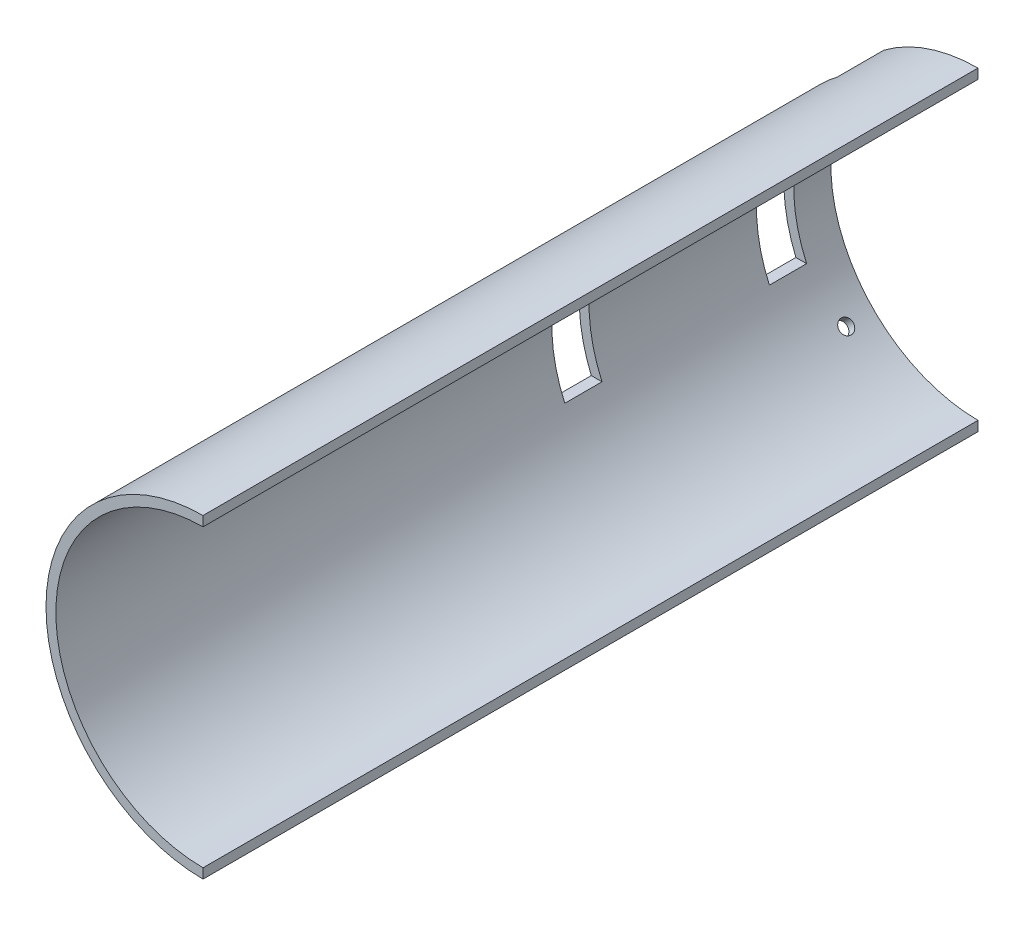
SolidWorks part; units mm, degrees
material "1060 Alloy"
ref_plane "Front Plane" through (0, 0, 0) normal (0, 0, 1) x (1, 0, 0)
ref_plane "Top Plane" through (0, 0, 0) normal (0, 1, 0) x (1, 0, 0)
ref_plane "Right Plane" through (0, 0, 0) normal (1, 0, 0) x (0, 0, -1)
sketch "Sketch1" plane through (0, 0, 0) normal (0, 0, 1) x (1, 0, 0)
  line L0 (0, 50.8) -> (0, 47.62)
  line L1 (0, -47.62) -> (0, -50.8)
  arc A0 (0, 50.8) -> (0, -50.8) centre (0, 0) ccw
  arc A1 (0, 47.62) -> (0, -47.62) centre (0, 0) ccw
  circle A2 centre (0, 0) radius 50.8 construction
  circle A3 centre (0, 0) radius 47.62 construction
  dimension "D1" = 101.6
  dimension "D2" = 3.18
extrude "Boss-Extrude1" add sketch "Sketch1" along normal blind 250
ref_plane "Plane1" through (-35.921, 35.921, 0) normal (-0.7071, 0.7071, 0) x (0, 0, -1)
ref_plane "Plane2" through (-35.921, -35.921, 0) normal (-0.7071, -0.7071, 0) x (0, 0, -1)
sketch "Sketch4" plane through (0, 0, 250) normal (0, 0, 1) x (1, 0, 0)
  line L0 (0, 0) -> (-35.921, 35.921)
  line L1 (-16.1645, 55.6776) -> (-55.6776, 16.1645) construction
  line L2 (0, 0) -> (-35.921, -35.921)
  arc A0 (0, 50.8) -> (0, -50.8) centre (0, 0) ccw construction
hole_wizard "M4 Clearance Hole1" positions "Sketch6" profile "Sketch5" hole size "M4" standard "ISO"
sketch "Sketch6" plane through (-35.921, 35.921, 0) normal (-0.7071, 0.7071, 0) x (0, 0, -1)
  line L1 (0, -35.921) -> (0, 50.8) construction
  point P0 (-9, 0)
  dimension "D1" = 9
sketch "Sketch5" plane through (-35.921, 35.921, 9) normal (0, 0, 1) x (-0.7071, -0.7071, 0)
  line L0 (0, 0) -> (0, 16.3519)
  line L1 (0, 16.3519) -> (2.25, 15)
  line L2 (2.25, 15) -> (2.25, 0)
  line L5 (2.25, 0) -> (0, 0)
  line L10 (0, 16.3519) -> (-2.25, 15) construction
  line L11 (0, -6.35) -> (0, 107.95) construction
  dimension "Hole Dia." = 4.5
  dimension "Hole Depth" = 15
  dimension "Drill Angle" = 118
hole_wizard "M4 Clearance Hole2" positions "Sketch8" profile "Sketch7" hole size "M4" standard "ISO"
sketch "Sketch8" plane through (-35.921, -35.921, 0) normal (-0.7071, -0.7071, 0) x (0, 0, -1)
  line L1 (0, -50.8) -> (0, 35.921) construction
  point P0 (-9, 0)
  dimension "D1" = 9
sketch "Sketch7" plane through (-35.921, -35.921, 9) normal (0, 0, 1) x (0.7071, -0.7071, 0)
  line L0 (0, 0) -> (0, 16.3519)
  line L1 (0, 16.3519) -> (2.25, 15)
  line L2 (2.25, 15) -> (2.25, 0)
  line L5 (2.25, 0) -> (0, 0)
  line L10 (0, 16.3519) -> (-2.25, 15) construction
  line L11 (0, -6.35) -> (0, 107.95) construction
  dimension "Hole Dia." = 4.5
  dimension "Hole Depth" = 15
  dimension "Drill Angle" = 118
ref_plane "Plane3" through (-50.8, 0, 0) normal (-1, 0, 0) x (0, 0, 1)
sketch "Sketch9" plane through (-50.8, 0, 0) normal (-1, 0, 0) x (0, 0, 1)
  line L0 (250, -50.8) -> (250, 50.8) construction
  line L1 (78, 19.5) -> (90, 19.5)
  line L2 (78, 19.5) -> (78, -19.5)
  line L3 (78, 0) -> (90, 0)
  line L4 (90, 19.5) -> (90, -19.5)
  line L5 (78, -19.5) -> (90, -19.5)
  line L6 (0, 0) -> (12, 0)
  line L7 (12, 0) -> (12, 19.5)
  line L8 (12, 19.5) -> (24, 19.5)
  line L9 (24, 19.5) -> (24, -19.5)
  line L10 (24, -19.5) -> (12, -19.5)
  line L11 (12, -19.5) -> (12, 0)
  dimension "D1" = 12
  dimension "D2" = 160
  dimension "D3" = 19.5
  dimension "D4" = 0
  dimension "D5" = 12
  dimension "D6" = 12
extrude "Cut-Extrude1" cut sketch "Sketch9" against normal blind 10 contours L4 L1 L2 L3 | L2 L5 L4 L3 | L11 L10 L9 L8 L7 region at (-50.8, 9.75, 84) region at (-50.8, -9.75, 84) region at (-50.8, 0, 18)
sketch "Sketch12" plane through (-35.921, 35.921, 0) normal (-0.7071, 0.7071, 0) x (0, 0, -1)
  line L0 (-6.75, 0) -> (0, 0)
  circle A0 centre (-9, 0) radius 2.25 construction
sketch "Sketch13" plane through (-35.921, -35.921, 0) normal (-0.7071, -0.7071, 0) x (0, 0, -1)
  line L0 (-6.75, 0) -> (0, 0)
  circle A0 centre (-9, 0) radius 2.25 construction
  circle A1 centre (-9, 0) radius 2.25 construction
sketch "Sketch14" plane through (0, 0, 0) normal (0, 0, -1) x (-1, 0, 0)
  line L0 (35.9241, 35.9179) -> (35.5706, 35.5644)
  line L1 (30.54, 40.5949) -> (40.5949, 30.54)
  line L3 (32.2061, 39.2833) -> (39.2833, 32.2061)
  arc A0 (0, -50.8) -> (0, 50.8) centre (0, 0) ccw construction
  arc A1 (39.2833, 32.2061) -> (32.2061, 39.2833) centre (0, 0) ccw
  circle A2 centre (0, 0) radius 50.8
  arc M2 (0, -50.8) -> (0, 50.8) centre (0, 0) ccw
  dimension "D1" = 0.5
extrude "Cut-Extrude2" cut sketch "Sketch14" against normal blind 15 contours L0 A1 L3 | L3 A1 L0 | A1 L3 L0 L1 M2 | A1 L0 L1 L3 M2 region at (-37.8387, 33.4665, 0) region at (-33.4697, 37.8356, 0) region at (-37.1437, 34.4854, 0) region at (-34.489, 37.1403, 0)
ref_axis "Axis1" through (0, 0, 250) along (0, 0, -1)
pattern_circular "CirPattern1" count 2 every 270 about axis through (0, 0, 250) along (0, 0, -1) of "Cut-Extrude2"
sketch "Sketch15" plane through (0, 0, 0) normal (0, 0, -1) x (-1, 0, 0)
  line L1 (0, 50.8) -> (0.15, 50.8)
  line L2 (0, 50.8) -> (0, -50.7998)
  line L4 (0.15, 50.8) -> (0.15, -50.7998)
  line L6 (0, -50.7998) -> (0, -50.8261)
  line L7 (0, -50.8261) -> (0.15, -50.8261)
  line L8 (0.15, -50.7998) -> (0.15, -50.8261)
  arc A0 (0, -50.8) -> (30.54, -40.5949) centre (0, 0) ccw construction
  dimension "D1" = 0.15
extrude "Cut-Extrude4" cut sketch "Sketch15" against normal through all
ref_plane "Plane4" through (-0.15, 0, 0) normal (1, 0, 0) x (0, 0, -1)
ref_plane "Plane5" through (0, 0, 0) normal (0, -1, 0) x (-1, 0, 0)
ref_axis "Axis2" through (-0.15, 0, 262.5) along (0, 0, -1)
